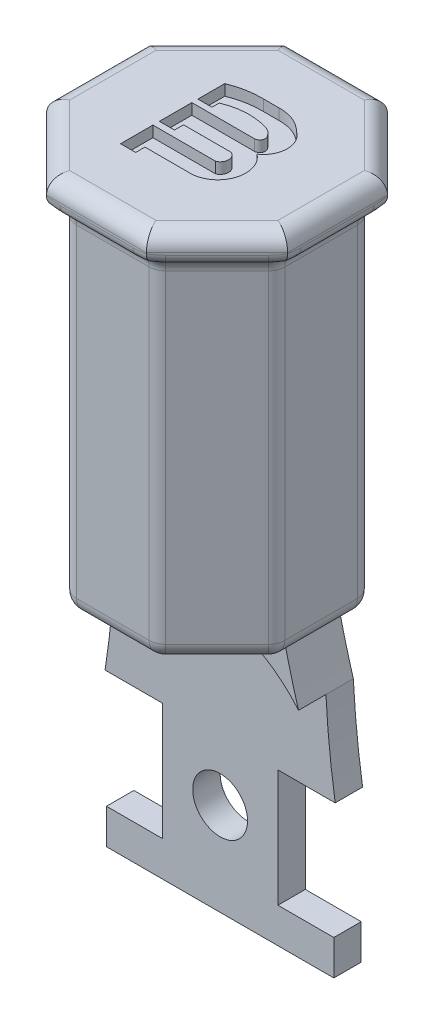
SolidWorks part; units mm, degrees
ref_plane "Front" through (0, 0, 0) normal (0, 0, 1) x (1, 0, 0)
ref_plane "Top" through (0, 0, 0) normal (0, 1, 0) x (1, 0, 0)
ref_plane "Right" through (0, 0, 0) normal (1, 0, 0) x (0, 0, -1)
sketch "Sketch1" plane through (0, 0, 0) normal (0, 0, 1) x (1, 0, 0)
  line L0 (0, -3.1917) -> (0, 49996.8083) construction
  line L1 (9.096, -3.1917) -> (-49990.904, -3.1917) construction
  line L2 (0, 0) -> (0, 111.1313) construction
  line L3 (-16.9424, -16.9424) -> (0, 0) construction
  line L4 (0, 111.1313) -> (16, 111.1313) construction
  line L5 (0, 111.1313) -> (0, 43.0505) construction
  line L6 (0, 111.1313) -> (-16, 111.1313) construction
  line L7 (0, 0) -> (0, -102.7303) construction
  line L8 (0, 0) -> (53.033, -53.033) construction
  line L9 (-20.9932, 10.8458) -> (-10.5429, 10.8458) construction
  line L10 (-10.5429, 10.8458) -> (-10.5429, -10.5429) construction
  line L11 (-10.5429, -10.5429) -> (-20.7412, -10.5429) construction
  line L12 (-20.7412, -10.5429) -> (-20.7412, -16.9424) construction
  line L13 (20.7412, -10.5429) -> (20.7412, -16.9424) construction
  line L14 (10.5429, -10.5429) -> (20.7412, -10.5429) construction
  line L15 (10.5429, 10.8458) -> (10.5429, -10.5429) construction
  line L16 (20.9932, 10.8458) -> (10.5429, 10.8458) construction
  line L17 (-20.7412, -16.9424) -> (20.7412, -16.9424) construction
  line L18 (0, 0) -> (-71.8792, -60.3138) construction
  line L19 (0, 0) -> (57.4533, -48.2091) construction
  line L20 (-20.9932, 10.8458) -> (-10.5429, 10.8458)
  line L21 (-10.5429, 10.8458) -> (-10.5429, -10.5429)
  line L22 (-10.5429, -10.5429) -> (-20.7412, -10.5429)
  line L23 (-20.7412, -10.5429) -> (-20.7412, -16.9424)
  line L24 (-20.7412, -16.9424) -> (20.7412, -16.9424)
  line L25 (20.7412, -16.9424) -> (20.7412, -10.5429)
  line L26 (20.7412, -10.5429) -> (10.5429, -10.5429)
  line L27 (10.5429, -10.5429) -> (10.5429, 10.8458)
  line L28 (10.5429, 10.8458) -> (20.9932, 10.8458)
  line L29 (0, -3.1917) -> (0, 39.0971) construction
  line L30 (0, 36.1313) -> (0, -16.9424) construction
  circle A0 centre (0, 0) radius 5
  arc A1 (-57.4533, -48.2091) -> (-16, 111.1313) centre (-134.4579, 56.8865) ccw construction
  arc A2 (57.4533, -48.2091) -> (16, 111.1313) centre (134.4579, 56.8865) cw construction
  arc A3 (-16, 111.1313) -> (16, 111.1313) centre (0, 85.2605) cw construction
  arc A4 (-20.9932, 10.8458) -> (-19.3031, 27.1387) centre (-179.4914, 35.5214) ccw
  arc A5 (20.9932, 10.8458) -> (19.3031, 27.1387) centre (179.4914, 35.5214) cw
  arc A6 (-19.3031, 27.1387) -> (19.3031, 27.1387) centre (0, 10.9174) cw
  arc A7 (-19.3031, 27.1387) -> (-16, 111.1313) centre (-183.0673, 75.6401) ccw
  arc A8 (19.3031, 27.1387) -> (16, 111.1313) centre (183.0673, 75.6401) cw
  arc A9 (-14.1382, 50.4592) -> (14.1382, 50.4592) centre (0, 41.7069) cw
  point P22 (-18.7517, -113.0155)
  dimension "D1" = 10
  dimension "D2" = 5
  dimension "D3" = 5
  dimension "D4" = 41.4824
  dimension "D5" = 21.3887
  dimension "D6" = 6.3996
  dimension "D7" = 21.0858
  dimension "D8" = 6.3995
  dimension "D9" = 36.1313
  dimension "D10" = 75
extrude "Boss-Extrude1" add sketch "Sketch1" along normal blind 5 contours A6 A4 L20 L21 L22 L23 L24 L25 L26 L27 L28 A5 A0 region at (0, 10.5519, 0)
sketch "Sketch2" [suppressed] plane through (0, 0, 0) normal (0, 0, 1) x (1, 0, 0)
  line L0 (0, -200003.1917) -> (0, 249996.8083) construction
  line L1 (0, -200003.1917) -> (0, 249996.8083)
  arc A0 (16, 111.1313) -> (19.3031, 27.1387) centre (183.0673, 75.6401) ccw construction
  arc A1 (-19.3031, 27.1387) -> (-16, 111.1313) centre (-183.0673, 75.6401) ccw construction
  arc A2 (19.3031, 27.1387) -> (-19.3031, 27.1387) centre (0, 10.9174) ccw construction
  arc A3 (16, 111.1313) -> (19.3031, 27.1387) centre (183.0673, 75.6401) ccw
  arc A4 (-19.3031, 27.1387) -> (-16, 111.1313) centre (-183.0673, 75.6401) ccw
  arc A5 (19.3031, 27.1387) -> (-19.3031, 27.1387) centre (0, 10.9174) ccw
ref_plane "Plane1" through (0, 36.1313, 0) normal (0, 1, 0) x (1, 0, 0)
sketch "Sketch3" plane through (0, 36.1313, 0) normal (0, 1, 0) x (1, 0, 0)
  line L0 (-20.7412, 0) -> (20.7412, 0) construction
  line L1 (19, 2.299) -> (7.8701, 13.4289)
  line L2 (7.8701, 13.4289) -> (-7.8701, 13.4289)
  line L3 (-7.8701, 13.4289) -> (-19, 2.299)
  line L4 (-19, 2.299) -> (-19, -13.4411)
  line L5 (-19, -13.4411) -> (-7.8701, -24.5711)
  line L6 (-7.8701, -24.5711) -> (7.8701, -24.5711)
  line L7 (7.8701, -24.5711) -> (19, -13.4411)
  line L8 (19, -13.4411) -> (19, 2.299)
  circle A0 centre (0, -5.5711) radius 19 construction
  dimension "D1" = 38
extrude "Boss-Extrude2" add sketch "Sketch3" along normal blind 65 separate body
sketch "Sketch4" plane through (0, 101.1313, 0) normal (0, 1, 0) x (1, 0, 0)
  line L0 (22, -14.6838) -> (22, 3.5416)
  line L1 (22, 3.5416) -> (9.1127, 16.4289)
  line L2 (9.1127, 16.4289) -> (-9.1127, 16.4289)
  line L3 (-9.1127, 16.4289) -> (-22, 3.5416)
  line L4 (-22, 3.5416) -> (-22, -14.6838)
  line L5 (-22, -14.6838) -> (-9.1127, -27.5711)
  line L6 (-9.1127, -27.5711) -> (9.1127, -27.5711)
  line L7 (9.1127, -27.5711) -> (22, -14.6838)
  line L8 (19, -13.4411) -> (19, 2.299)
  line L9 (19, 2.299) -> (7.8701, 13.4289)
  line L10 (7.8701, 13.4289) -> (-7.8701, 13.4289)
  line L11 (-7.8701, 13.4289) -> (-19, 2.299)
  line L12 (-19, 2.299) -> (-19, -13.4411)
  line L13 (-19, -13.4411) -> (-7.8701, -24.5711)
  line L14 (-7.8701, -24.5711) -> (7.8701, -24.5711)
  line L15 (7.8701, -24.5711) -> (19, -13.4411)
  line L16 (19, -13.4411) -> (19, 2.299)
  line L17 (19, 2.299) -> (7.8701, 13.4289)
  line L18 (7.8701, 13.4289) -> (-7.8701, 13.4289)
  line L19 (-7.8701, 13.4289) -> (-19, 2.299)
  line L20 (-19, 2.299) -> (-19, -13.4411)
  line L21 (-19, -13.4411) -> (-7.8701, -24.5711)
  line L22 (-7.8701, -24.5711) -> (7.8701, -24.5711)
  line L23 (7.8701, -24.5711) -> (19, -13.4411)
  dimension "D1" = 0
  dimension "D2" = 3
extrude "Boss-Extrude3" add sketch "Sketch4" along normal blind 5 contours L0 L1 L2 L3 L4 L5 L6 L7
fillet "Fillet1" radius 3 32 edges at (-19, 101.1313, 5.5711) (-19, 36.1313, 5.5711) (-19, 68.6313, 13.4411) (-13.435, 101.1313, 19.0061) (-13.435, 36.1313, 19.0061) (13.435, 101.1313, 19.0061) (13.435, 36.1313, 19.0061) (19, 68.6313, 13.4411) (19, 101.1313, 5.5711) (19, 36.1313, 5.5711) (0, 101.1313, -13.4289) (0, 36.1313, -13.4289) (19, 68.6313, -2.299) (13.435, 101.1313, -7.8639) (7.8701, 68.6313, -13.4289) (13.435, 36.1313, -7.8639) (-7.8701, 68.6313, -13.4289) (-13.435, 101.1313, -7.8639) (-19, 68.6313, -2.299) (-13.435, 36.1313, -7.8639) (-7.8701, 68.6313, 24.5711) (0, 101.1313, 24.5711) (7.8701, 68.6313, 24.5711) (0, 36.1313, 24.5711) (0, 106.1313, 27.5711) (-15.5563, 106.1313, 21.1274) (-22, 106.1313, 5.5711) (-15.5563, 106.1313, -9.9853) (0, 106.1313, -16.4289) (15.5563, 106.1313, -9.9853) (22, 106.1313, 5.5711) (15.5563, 106.1313, 21.1274)
sketch "Sketch5" plane through (0, 0, 0) normal (0, 0, 1) x (1, 0, 0)
  arc A0 (16, 111.1313) -> (19.3031, 27.1387) centre (183.0673, 75.6401) ccw construction
  arc A1 (-19.3031, 27.1387) -> (-16, 111.1313) centre (-183.0673, 75.6401) ccw construction
  arc A2 (14.1382, 50.4592) -> (-14.1382, 50.4592) centre (0, 41.7069) ccw construction
  arc A3 (19.3031, 27.1387) -> (-19.3031, 27.1387) centre (0, 10.9174) ccw construction
  arc A4 (14.1382, 50.4592) -> (19.3031, 27.1387) centre (183.0673, 75.6401) ccw
  arc A5 (-19.3031, 27.1387) -> (-14.1382, 50.4592) centre (-183.0673, 75.6401) ccw
  arc A6 (14.1382, 50.4592) -> (-14.1382, 50.4592) centre (0, 41.7069) ccw
  arc A7 (19.3031, 27.1387) -> (-19.3031, 27.1387) centre (0, 10.9174) ccw
extrude "Boss-Extrude6" add sketch "Sketch5" along normal blind 10
sketch "Sketch6" plane through (0, 106.1313, 0) normal (0, 1, 0) x (1, 0, 0)
  line L0 (-7.4635, 3.3075) -> (-7.4635, -1.5941)
  line L1 (-7.4635, -1.5941) -> (-4.903, -1.5941)
  line L2 (-4.903, -1.5941) -> (-4.903, -0.2772)
  line L3 (3.9591, -2.6963) -> (-7.4635, -2.6963)
  line L4 (-7.4635, -2.6963) -> (-7.4635, -8.6196)
  line L5 (-7.4635, -8.6196) -> (-4.7057, -8.6196)
  line L6 (-4.7057, -8.6196) -> (-4.7057, -6.9679)
  line L7 (-4.7057, -6.9679) -> (3.9591, -6.9679)
  line L8 (-7.4635, -9.7997) -> (3.9591, -9.7997)
  line L9 (-7.4635, -9.7997) -> (-7.4635, -15.7042)
  line L10 (-7.4635, -15.7042) -> (-4.7057, -15.7042)
  line L11 (-4.7057, -15.7042) -> (-4.7057, -14.0117)
  line L12 (-4.7057, -14.0117) -> (3.9591, -14.0117)
  line L13 (-1.4822, 4.4174) -> (1.3263, 4.4174)
  arc A0 (-4.903, -0.2772) -> (3.3436, 0.0526) centre (-0.3447, -10.9858) cw
  arc A1 (3.9591, -2.6963) -> (4.6155, -0.9594) centre (3.9335, -1.6941) ccw
  arc A2 (3.3436, 0.0526) -> (4.6155, -0.9594) centre (2.5033, -2.3087) cw
  arc A3 (3.9591, -6.9679) -> (3.9591, -9.7997) centre (3.4158, -8.3838) cw
  arc A4 (3.9591, -14.0117) -> (6.6314, -4.895) centre (3.503, -8.928) ccw
  arc A5 (-7.4635, 3.3075) -> (-1.4822, 4.4174) centre (-1.8662, -10.1848) cw
  arc A6 (6.6314, -4.895) -> (6.6314, 2.3056) centre (4.2015, -1.2947) ccw
  arc A7 (1.3263, 4.4174) -> (6.6314, 2.3056) centre (1.5427, -2.7583) cw
extrude "Cut-Extrude1" cut sketch "Sketch6" against normal blind 2
fillet "Fillet2" radius 2 8 edges at (-22, 101.1313, 5.5711) (-15.5563, 101.1313, -9.9853) (0, 101.1313, -16.4289) (15.5563, 101.1313, -9.9853) (22, 101.1313, 5.5711) (15.5563, 101.1313, 21.1274) (0, 101.1313, 27.5711) (-15.5563, 101.1313, 21.1274)
